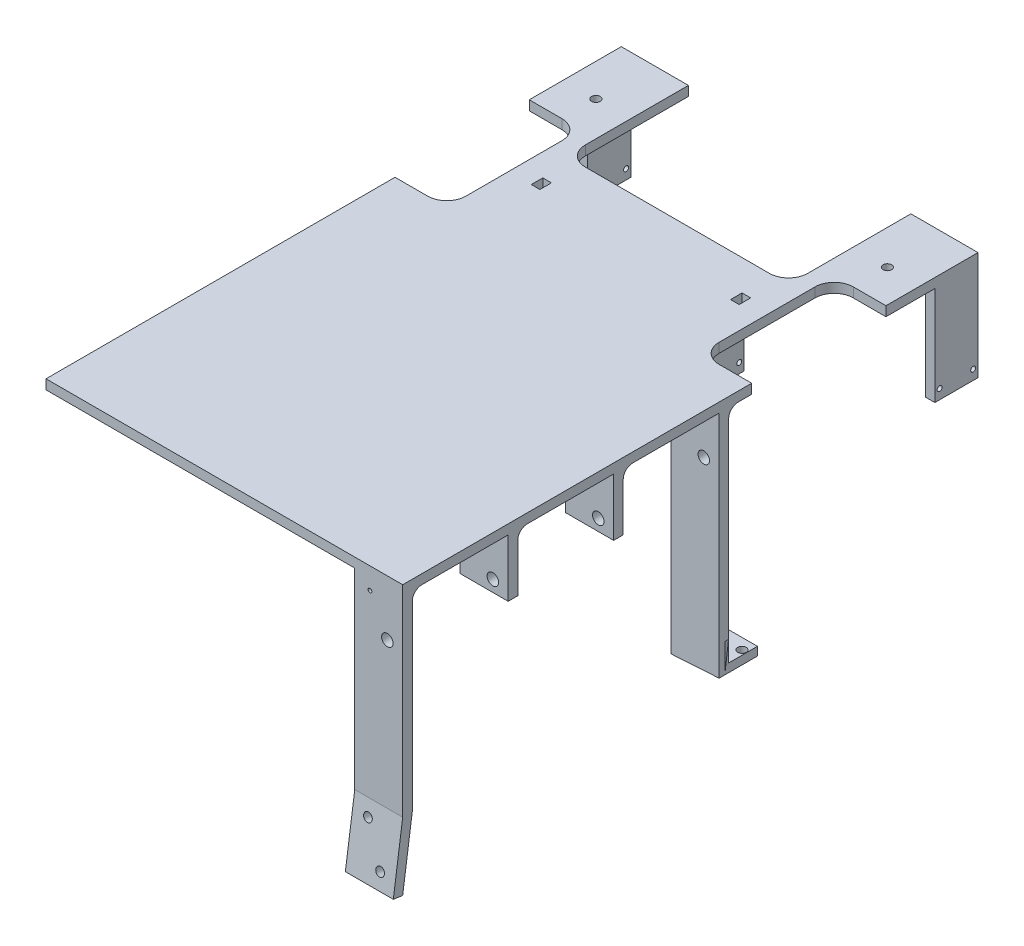
SolidWorks part; units mm, degrees
ref_plane "Front Plane" through (0, 0, 0) normal (0, 0, 1) x (1, 0, 0)
ref_plane "Top Plane" through (0, 0, 0) normal (0, 1, 0) x (1, 0, 0)
ref_plane "Right Plane" through (0, 0, 0) normal (1, 0, 0) x (0, 0, -1)
sketch "Sketch1" plane through (0, 0, 0) normal (0, 1, 0) x (1, 0, 0)
  line L0 (0, 0) -> (0, -300)
  line L1 (0, -300) -> (186, -300)
  line L2 (186, -300) -> (186, 0)
  line L3 (186, 0) -> (176, 0)
  line L4 (176, 0) -> (151, 0)
  line L5 (151, 0) -> (151, -56.1159)
  line L6 (151, -56.1159) -> (35, -56.1159)
  line L7 (35, -56.1159) -> (35, 0)
  line L8 (35, 0) -> (10, 0)
  line L9 (10, 0) -> (0, 0)
  line L10 (93, -300) -> (93, -56.1159) construction
  point P9 (93, -56.1159)
  dimension "D1" = 300
  dimension "D2" = 10
  dimension "D3" = 186
  dimension "D5" = 10
  dimension "D6" = 35
extrude "Boss-Extrude1" add sketch "Sketch1" along normal blind 5
sketch "Sketch2" plane through (0, 0, 0) normal (0, -1, 0) x (1, 0, 0)
  line L1 (50.5, 94) -> (55.5, 94)
  line L2 (50.5, 94) -> (50.5, 71.5)
  line L3 (50.5, 71.5) -> (55.5, 71.5)
  line L4 (55.5, 94) -> (55.5, 71.5)
  line L6 (135.5, 94) -> (130.5, 94)
  line L7 (135.5, 94) -> (135.5, 71.5)
  line L8 (135.5, 71.5) -> (130.5, 71.5)
  line L9 (130.5, 94) -> (130.5, 71.5)
  line L10 (0, 300) -> (186, 300) construction
  line L11 (186, 300) -> (186, 0) construction
  line L12 (0, 0) -> (0, 300) construction
  dimension "D1" = 5
  dimension "D2" = 22.5
  dimension "D3" = 5
  dimension "D4" = 206
  dimension "D5" = 22.5
  dimension "D6" = 50.5
  dimension "D7" = 50.5
extrude "Boss-Extrude2" add sketch "Sketch2" along normal blind 38
sketch "Sketch5" plane through (0, 0, 0) normal (0, -1, 0) x (1, 0, 0)
  line L0 (186, 300) -> (186, 0) construction
  line L1 (186, 295) -> (161, 295)
  line L2 (186, 295) -> (186, 300)
  line L3 (186, 300) -> (161, 300)
  line L4 (161, 295) -> (161, 300)
  line L5 (0, 300) -> (186, 300) construction
  line L6 (186, 240) -> (161, 240)
  line L7 (186, 240) -> (186, 245)
  line L8 (186, 245) -> (161, 245)
  line L9 (161, 240) -> (161, 245)
  line L10 (186, 185) -> (161, 185)
  line L11 (186, 185) -> (186, 190)
  line L12 (186, 190) -> (161, 190)
  line L13 (161, 185) -> (161, 190)
  line L14 (186, 130) -> (161, 130)
  line L15 (186, 130) -> (186, 135)
  line L16 (186, 135) -> (161, 135)
  line L17 (161, 130) -> (161, 135)
  dimension "D1" = 5
  dimension "D2" = 5
  dimension "D3" = 5
  dimension "D4" = 5
  dimension "D5" = 50
  dimension "D6" = 50
  dimension "D7" = 50
  dimension "D8" = 25
extrude "Boss-Extrude3" add sketch "Sketch5" along normal blind 30
fillet "Fillet3" radius 5 4 edges at (173.5, 0, 130) (173.5, 0, 185) (173.5, 0, 240) (173.5, 0, 295)
sketch "Sketch6" plane through (0, 0, 300) normal (0, 0, 1) x (1, 0, 0)
  line L0 (186, -30) -> (161, -30) construction
  line L1 (186, 5) -> (186, -30) construction
  circle A0 centre (178, -24) radius 3
  dimension "D1" = 6
  dimension "D2" = 6
  dimension "D3" = 8
extrude "Cut-Extrude4" cut sketch "Sketch6" against normal blind 172
sketch "Sketch7" plane through (0, 0, 0) normal (0, -1, 0) x (1, 0, 0)
  line L0 (0, 0) -> (0, 300) construction
  line L1 (0, 22.5) -> (5, 22.5)
  line L2 (0, 22.5) -> (0, 0)
  line L3 (0, 0) -> (5, 0)
  line L4 (5, 22.5) -> (5, 0)
  line L5 (186, 125) -> (186, 0) construction
  line L6 (186, 22.5) -> (181, 22.5)
  line L7 (186, 22.5) -> (186, 0)
  line L8 (186, 0) -> (181, 0)
  line L9 (181, 22.5) -> (181, 0)
  line L10 (186, 0) -> (151, 0) construction
  dimension "D1" = 5
  dimension "D2" = 5
  dimension "D3" = 22.5
  dimension "D4" = 22.5
extrude "Boss-Extrude4" add sketch "Sketch7" along normal blind 51.5
sketch "Sketch3" plane through (186, 0, 0) normal (1, 0, 0) x (0, 0, -1)
  line L4 (-71.5, 0) -> (-94, 0)
  line L5 (-71.5, -38) -> (-71.5, 0)
  line L6 (-94, -38) -> (-71.5, -38)
  line L7 (-94, 0) -> (-94, -38)
  line L9 (-71.5, -38) -> (-71.5, 0)
  line L10 (-94, -38) -> (-71.5, -38)
  line L11 (-94, 0) -> (-94, -38)
  line L13 (-71.5, 0) -> (-94, 0)
  circle A0 centre (-74, -32.9) radius 1.3 construction
  circle A1 centre (-91.5, -32.9) radius 1.3 construction
  circle A2 centre (-74, -32.9) radius 1.3
  circle A3 centre (-91.5, -32.9) radius 1.3
  circle A4 centre (-20, -46.4) radius 1.3 construction
  circle A5 centre (-2.5, -46.4) radius 1.3 construction
  circle A6 centre (-20, -46.4) radius 1.3
  circle A7 centre (-2.5, -46.4) radius 1.3
  dimension "D1" = 0
extrude "Cut-Extrude2" cut sketch "Sketch3" against normal through all contours A3 | A2 | A6 | A7
sketch "Sketch9" plane through (0, 0, 0) normal (0, -1, 0) x (1, 0, 0)
  line L0 (35, 0) -> (5, 0) construction
  line L1 (35, 0) -> (151, 0)
  line L2 (35, 0) -> (35, 63.7796)
  line L3 (35, 63.7796) -> (151, 63.7796)
  line L4 (151, 0) -> (151, 63.7796)
  line L5 (35, 56.1159) -> (35, 0) construction
  line L6 (151, 0) -> (151, 56.1159) construction
extrude "Cut-Extrude6" cut sketch "Sketch9" against normal blind 10
sketch "Sketch10" plane through (0, -30, 0) normal (0, -1, 0) x (1, 0, 0)
  line L1 (186, 295) -> (161, 295)
  line L2 (186, 295) -> (186, 300)
  line L3 (186, 300) -> (161, 300)
  line L4 (161, 295) -> (161, 300)
  line L5 (161, 130) -> (186, 130)
  line L6 (161, 130) -> (161, 135)
  line L7 (161, 135) -> (186, 135)
  line L8 (186, 130) -> (186, 135)
extrude "Boss-Extrude5" add sketch "Sketch10" along normal blind 70
sketch "Sketch11" plane through (186, 0, 0) normal (1, 0, 0) x (0, 0, -1)
  line L0 (-300, -100) -> (-304.9019, -134.6439)
  line L1 (-304.9019, -134.6439) -> (-300, -135.3374)
  line L2 (-300, -135.3374) -> (-295, -100)
  line L3 (-300, -100) -> (-295, -100)
extrude "Boss-Extrude6" add sketch "Sketch11" against normal blind 25
sketch "Sketch12" plane through (0, -100, 0) normal (0, -1, 0) x (1, 0, 0)
  line L1 (161, 130) -> (186, 130)
  line L2 (161, 130) -> (161, 135)
  line L3 (161, 135) -> (186, 135)
  line L4 (186, 130) -> (186, 135)
extrude "Boss-Extrude7" add sketch "Sketch12" along normal blind 19.72
sketch "Sketch13" plane through (0, 0, 130) normal (0, 0, -1) x (-1, 0, 0)
  line L0 (-186, -115.3141) -> (-186, -119.72)
  line L1 (-186, -119.72) -> (-186, -5) construction
  line L2 (-186, -119.72) -> (-161, -121.2619)
  line L3 (-161, -121.2619) -> (-161, -115.3141)
  line L4 (-161, -115.3141) -> (-186, -115.3141)
  line L5 (-161, -119.72) -> (-161, -5) construction
  line L8 (-88.7239, -126.5865) -> (-200, -119.7234) construction
extrude "Boss-Extrude8" add sketch "Sketch13" along normal blind 15 and the other way blind 5
sketch "Sketch14" plane through (8.0608, -130.6946, 0) normal (0.0616, -0.9981, 0) x (0.9981, 0.0616, 0)
  line L0 (186.3576, 115) -> (178.2774, 132.0374)
  line L1 (178.2774, 115) -> (153.2299, 115) construction
  line L2 (178.2774, 115) -> (178.2774, 135) construction
  line L3 (178.2774, 132.0374) -> (198.0152, 130.431)
  line L4 (198.0152, 130.431) -> (197.5151, 111.3666)
  line L5 (197.5151, 111.3666) -> (186.3576, 109.6075)
  line L6 (186.3576, 109.6075) -> (186.3576, 115)
extrude "Cut-Extrude7" cut sketch "Sketch14" against normal blind 15
sketch "Sketch15" plane through (0, 39.652, 280.2402) normal (0, 0.1401, 0.9901) x (1, 0, 0)
  line L1 (161, -141.043) -> (161, -176.032) construction
  line L2 (186, -141.043) -> (161, -141.043) construction
  line L3 (186, -141.043) -> (186, -176.032) construction
  line L4 (161, -176.032) -> (186, -176.032) construction
  circle A0 centre (178, -168.032) radius 2.25
  circle A1 centre (169, -149.043) radius 2.25
  dimension "D1" = 4.5
  dimension "D2" = 4.5
  dimension "D3" = 8
  dimension "D4" = 8
  dimension "D5" = 8
  dimension "D6" = 8
extrude "Cut-Extrude8" cut sketch "Sketch15" against normal blind 20
sketch "Sketch16" plane through (0, 0, 0) normal (0, -1, 0) x (1, 0, 0)
  line L1 (166, 272) -> (172, 272)
  line L2 (166, 272) -> (166, 275)
  line L3 (166, 275) -> (172, 275)
  line L4 (172, 272) -> (172, 275)
  line L5 (143.4, 274.097) -> (137.4, 274.097)
  line L6 (143.4, 274.097) -> (143.4, 277.097)
  line L7 (143.4, 277.097) -> (137.4, 277.097)
  line L8 (137.4, 274.097) -> (137.4, 277.097)
  line L9 (166, 217) -> (172, 217)
  line L10 (166, 217) -> (166, 220)
  line L11 (166, 220) -> (172, 220)
  line L12 (172, 217) -> (172, 220)
  line L13 (166, 162) -> (172, 162)
  line L14 (166, 162) -> (166, 165)
  line L15 (166, 165) -> (172, 165)
  line L16 (172, 162) -> (172, 165)
  line L17 (137.4, 218.7302) -> (143.4, 218.7302)
  line L18 (137.4, 218.7302) -> (137.4, 221.7302)
  line L19 (137.4, 221.7302) -> (143.4, 221.7302)
  line L20 (143.4, 218.7302) -> (143.4, 221.7302)
  line L21 (137.4, 164.526) -> (143.4, 164.526)
  line L22 (137.4, 164.526) -> (137.4, 167.526)
  line L23 (137.4, 167.526) -> (143.4, 167.526)
  line L24 (143.4, 164.526) -> (143.4, 167.526)
  line L25 (186, 180) -> (186, 135) construction
  line L28 (161, 295) -> (186, 295) construction
  line L29 (161, 240) -> (186, 240) construction
  line L30 (161, 185) -> (186, 185) construction
  dimension "D1" = 3
  dimension "D2" = 3
  dimension "D3" = 3
  dimension "D4" = 3
  dimension "D5" = 3
  dimension "D6" = 3
  dimension "D7" = 20
  dimension "D8" = 22.6
  dimension "D9" = 6
  dimension "D10" = 6
  dimension "D11" = 23
  dimension "D12" = 23
  dimension "D13" = 23
extrude "Boss-Extrude9" add sketch "Sketch16" along normal blind 12.4
sketch "Sketch17" plane through (0, 0, 162) normal (0, 0, -1) x (-1, 0, 0)
  arc A0 (-169.75, -6.8) -> (-169.75, -5.6) centre (-168.95, -6.2) ccw construction
  arc A1 (-169.75, -6.8) -> (-169.75, -5.6) centre (-168.95, -6.2) ccw
  circle A2 centre (-168.95, -6.2) radius 1
  circle A3 centre (-140.45, -6.2) radius 1
extrude "Cut-Extrude9" cut sketch "Sketch17" against normal through all contours A1 A2 | A3 region at (168.95, -6.2, 162)
fillet "Fillet4" radius 5 6 edges at (140.4, 0, 277.097) (169, 0, 275) (140.4, 0, 221.7302) (169, 0, 220) (140.4, 0, 167.526) (169, 0, 165)
sketch "Sketch18" plane through (0, -115.3141, 0) normal (0, 1, 0) x (1, 0, 0)
  circle A0 centre (183.5318, -120.6471) radius 2.25
  dimension "D1" = 4.5
extrude "Cut-Extrude10" cut sketch "Sketch18" against normal through all
sketch "Sketch19" plane through (0, 0, 0) normal (0, -1, 0) x (1, 0, 0)
  line L0 (42.3, 80.75) -> (39.8, 80.75) construction
  line L1 (39.8, 84.75) -> (39.8, 80.75) construction
  line L2 (42.3, 84.75) -> (42.3, 80.75) construction
  line L3 (39.8, 84.75) -> (42.3, 84.75) construction
  line L4 (42.3, 80.75) -> (39.8, 80.75) construction
  line L5 (39.8, 84.75) -> (39.8, 80.75) construction
  line L6 (42.3, 84.75) -> (42.3, 80.75) construction
  line L7 (39.8, 84.75) -> (42.3, 84.75) construction
  line L8 (143.7, 80.75) -> (143.7, 84.75) construction
  line L9 (143.7, 84.75) -> (146.2, 84.75) construction
  line L10 (146.2, 80.75) -> (146.2, 84.75) construction
  line L11 (146.2, 80.75) -> (143.7, 80.75) construction
  line L12 (143.7, 80.75) -> (143.7, 84.75) construction
  line L13 (143.7, 84.75) -> (146.2, 84.75) construction
  line L14 (146.2, 80.75) -> (146.2, 84.75) construction
  line L15 (146.2, 80.75) -> (143.7, 80.75) construction
  line L16 (43.3, 79.75) -> (38.8, 79.75)
  line L17 (38.8, 85.75) -> (38.8, 79.75)
  line L18 (38.8, 85.75) -> (43.3, 85.75)
  line L19 (43.3, 85.75) -> (43.3, 79.75)
  line L20 (142.7, 79.75) -> (142.7, 85.75)
  line L21 (142.7, 85.75) -> (147.2, 85.75)
  line L22 (147.2, 79.75) -> (147.2, 85.75)
  line L23 (147.2, 79.75) -> (142.7, 79.75)
  line L31 (151, 0) -> (181, 0)
  line L32 (181, 0) -> (181, 22.5)
  line L34 (186, 22.5) -> (186, 125)
  line L35 (186, 125) -> (161, 125)
  line L36 (161, 125) -> (161, 135)
  line L37 (161, 135) -> (186, 135)
  line L38 (186, 135) -> (186, 180)
  line L39 (186, 180) -> (161, 180)
  line L40 (161, 180) -> (161, 190)
  line L41 (161, 190) -> (186, 190)
  line L42 (186, 190) -> (186, 235)
  line L43 (186, 235) -> (161, 235)
  line L44 (161, 235) -> (161, 245)
  line L45 (161, 245) -> (186, 245)
  line L46 (186, 245) -> (186, 290)
  line L47 (186, 290) -> (161, 290)
  line L48 (161, 290) -> (161, 300)
  line L49 (161, 300) -> (0, 300)
  line L50 (0, 300) -> (0, 22.5)
  line L51 (0, 22.5) -> (5, 22.5)
  line L52 (5, 22.5) -> (5, 0)
  line L53 (5, 0) -> (35, 0)
  line L56 (151, 63.7796) -> (151, 0)
  line L57 (151, 63.7796) -> (151, 0)
  line L58 (35, 0) -> (35, 63.7796)
  line L61 (151, 0) -> (181, 0)
  line L64 (186, 22.5) -> (186, 125)
  line L65 (186, 125) -> (161, 125)
  line L66 (161, 125) -> (161, 135)
  line L67 (161, 135) -> (186, 135)
  line L68 (186, 135) -> (186, 180)
  line L69 (186, 180) -> (161, 180)
  line L70 (161, 180) -> (161, 190)
  line L71 (161, 190) -> (186, 190)
  line L72 (186, 190) -> (186, 235)
  line L73 (186, 235) -> (161, 235)
  line L74 (161, 235) -> (161, 245)
  line L75 (161, 245) -> (186, 245)
  line L76 (186, 245) -> (186, 290)
  line L77 (186, 290) -> (161, 290)
  line L78 (161, 290) -> (161, 300)
  line L79 (161, 300) -> (0, 300)
  line L80 (0, 300) -> (0, 22.5)
  line L81 (0, 22.5) -> (5, 22.5)
  line L82 (5, 22.5) -> (5, 0)
  line L83 (5, 0) -> (35, 0)
  line L106 (35, 0) -> (35, 63.7796)
  line L107 (35, 63.7796) -> (151, 63.7796)
  line L108 (35, 63.7796) -> (151, 63.7796)
  line L116 (181, 22.5) -> (186, 22.5)
  line L122 (181, 22.5) -> (186, 22.5)
  line L124 (181, 0) -> (181, 22.5)
  dimension "D1" = 0
  dimension "D2" = 1
  dimension "D3" = 1
extrude "Cut-Extrude12" cut sketch "Sketch19" against normal through all contours L23 L22 L21 L20 | L19 L18 L17 L16 region at (41.05, 0, 82.75) region at (144.95, 0, 82.75)
sketch "Sketch20" plane through (0, 0, 0) normal (0, -1, 0) x (1, 0, 0)
  line L26 (151, 63.7796) -> (151, 0)
  line L27 (151, 63.7796) -> (151, 0)
  line L28 (35, 0) -> (35, 63.7796)
  line L29 (35, 0) -> (35, 63.7796)
  line L30 (35, 63.7796) -> (151, 63.7796)
  line L31 (151, 0) -> (181, 0)
  line L32 (181, 0) -> (181, 22.5)
  line L34 (186, 22.5) -> (186, 125)
  line L35 (186, 125) -> (161, 125)
  line L36 (161, 125) -> (161, 135)
  line L37 (161, 135) -> (186, 135)
  line L38 (186, 135) -> (186, 180)
  line L39 (186, 180) -> (161, 180)
  line L40 (161, 180) -> (161, 190)
  line L41 (161, 190) -> (186, 190)
  line L42 (186, 190) -> (186, 235)
  line L43 (186, 235) -> (161, 235)
  line L44 (161, 235) -> (161, 245)
  line L45 (161, 245) -> (186, 245)
  line L46 (186, 245) -> (186, 290)
  line L47 (186, 290) -> (161, 290)
  line L48 (161, 290) -> (161, 300)
  line L49 (161, 300) -> (0, 300)
  line L50 (0, 300) -> (0, 22.5)
  line L51 (0, 22.5) -> (5, 22.5)
  line L52 (5, 22.5) -> (5, 0)
  line L53 (5, 0) -> (35, 0)
  line L55 (35, 63.7796) -> (151, 63.7796)
  line L61 (151, 0) -> (181, 0)
  line L64 (186, 22.5) -> (186, 125)
  line L65 (186, 125) -> (161, 125)
  line L66 (161, 125) -> (161, 135)
  line L67 (161, 135) -> (186, 135)
  line L68 (186, 135) -> (186, 180)
  line L69 (186, 180) -> (161, 180)
  line L70 (161, 180) -> (161, 190)
  line L71 (161, 190) -> (186, 190)
  line L72 (186, 190) -> (186, 235)
  line L73 (186, 235) -> (161, 235)
  line L74 (161, 235) -> (161, 245)
  line L75 (161, 245) -> (186, 245)
  line L76 (186, 245) -> (186, 290)
  line L77 (186, 290) -> (161, 290)
  line L78 (161, 290) -> (161, 300)
  line L79 (161, 300) -> (0, 300)
  line L80 (0, 300) -> (0, 22.5)
  line L81 (0, 22.5) -> (5, 22.5)
  line L82 (5, 22.5) -> (5, 0)
  line L83 (5, 0) -> (35, 0)
  line L92 (181, 22.5) -> (186, 22.5)
  line L98 (181, 22.5) -> (186, 22.5)
  line L100 (181, 0) -> (181, 22.5)
  circle A0 centre (169, 30.25) radius 2.25 construction
  circle A1 centre (169, 55.25) radius 2.25 construction
  circle A2 centre (169, 30.25) radius 2.25
  circle A3 centre (169, 55.25) radius 2.25
  circle A4 centre (17, 55.25) radius 2.25 construction
  circle A5 centre (17, 30.25) radius 2.25 construction
  circle A6 centre (17, 55.25) radius 2.25
  circle A7 centre (17, 30.25) radius 2.25
  dimension "D1" = 0
extrude "Cut-Extrude13" cut sketch "Sketch20" against normal through all contours A3 | A6 | A7 | A2 region at (169, 0, 55.25)
fillet "Fillet6" radius 10 2 edges at (151, 2.5, 63.7796) (35, 2.5, 63.7796)
sketch "Sketch21" plane through (0, 0, 0) normal (0, -1, 0) x (1, 0, 0)
  line L0 (0, 22.5) -> (0, 300) construction
  line L1 (0, 48) -> (27, 48)
  line L2 (0, 48) -> (0, 118)
  line L3 (0, 118) -> (27, 118)
  line L4 (27, 48) -> (27, 118)
  line L5 (186, 125) -> (186, 22.5) construction
  line L6 (186, 48) -> (159, 48)
  line L7 (186, 48) -> (186, 118)
  line L8 (186, 118) -> (159, 118)
  line L9 (159, 48) -> (159, 118)
  line L10 (0, 300) -> (161, 300) construction
  dimension "D1" = 70
  dimension "D2" = 182
  dimension "D3" = 70
  dimension "D4" = 182
  dimension "D5" = 27
  dimension "D6" = 27
extrude "Cut-Extrude14" cut sketch "Sketch21" against normal through all
fillet "Fillet7" radius 10 4 edges at (27, 2.5, 118) (27, 2.5, 48) (159, 2.5, 48) (159, 2.5, 118)
